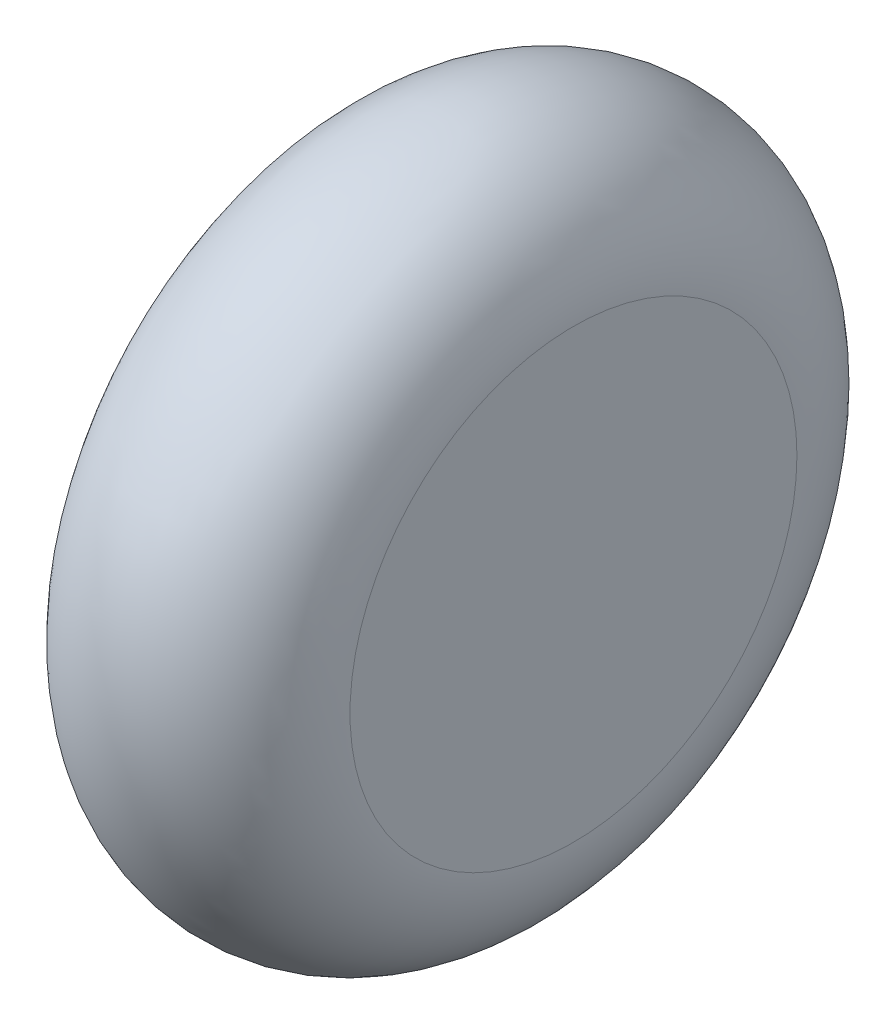
SolidWorks part; units mm, degrees
material "PW90:Mi:0:12:C1:0:1:2:Re:26:"
ref_plane "Front" through (0, 0, 0) normal (0, 0, 1) x (1, 0, 0)
ref_plane "Top" through (0, 0, 0) normal (0, 1, 0) x (1, 0, 0)
ref_plane "Right" through (0, 0, 0) normal (1, 0, 0) x (0, 0, -1)
sketch "Sketch1" plane through (0, 0, 0) normal (1, 0, 0) x (0, 0, -1)
  circle A0 centre (0, 0) radius 12.7
  dimension "D1" = 25.4
extrude "Boss-Extrude1" add sketch "Sketch1" along normal mid plane 9.144
fillet "Fillet1" 2 edges at (4.572, 0, -12.7) (-4.572, 0, -12.7) type full round first side face at (4.572, 0, -12.7) second side face at (-4.572, 0, -12.7) middle face at (4.572, 0, -12.7)
